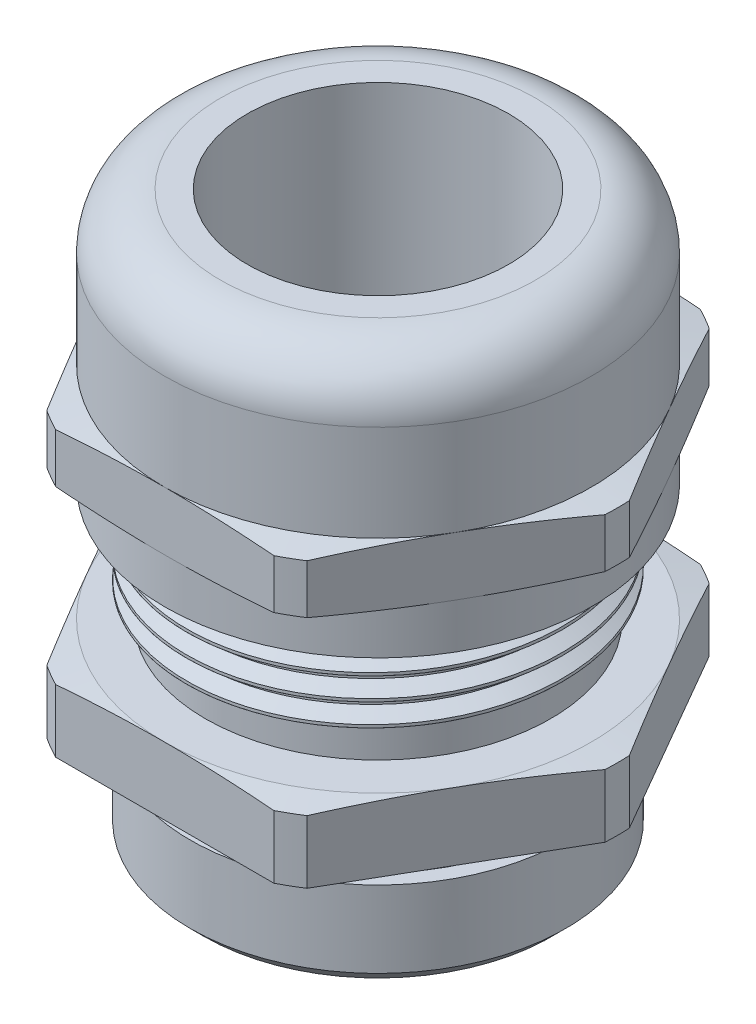
SolidWorks part; units mm, degrees
note: '?' marks a value the reader was unsure of.
material "Brass"
ref_plane "Front Plane" through (0, 0, 0) normal (0, 0, 1) x (1, 0, 0)
ref_plane "Top Plane" through (0, 0, 0) normal (0, 1, 0) x (1, 0, 0)
ref_plane "Right Plane" through (0, 0, 0) normal (1, 0, 0) x (0, 0, -1)
sketch "Sketch1" plane through (0, 0, 0) normal (0, 0, 1) x (1, 0, 0)
  line L0 (0, 0) -> (0, 40.2074) construction
  line L1 (-8.7, 34.6391) -> (-10.5, 34.6391)
  line L2 (-14.2, 30.9391) -> (-14.2, 24.5391)
  line L3 (-14.2, 24.5391) -> (-15.95, 24.2306)
  line L4 (-15.95, 24.2306) -> (-15.95, 20.9477)
  line L5 (-15.95, 20.9477) -> (-14.2, 20.6391)
  line L6 (-14.2, 20.6391) -> (-14.2, 17.6391)
  line L7 (-14.2, 17.6391) -> (-12.6, 17.6391)
  line L8 (-12.5, 19.6391) -> (-12.5, 11.8391)
  line L9 (-14.2, 9.8391) -> (-11.5, 9.8391)
  line L10 (-15.95, 9.5306) -> (-15.95, 5.3391)
  line L11 (-15.95, 5.3391) -> (-11.5, 5.3391)
  line L12 (-12.5, 3.3391) -> (-12.5, -2.6609)
  line L13 (-12.5, -2.6609) -> (-10, -2.6609)
  line L14 (-10, -2.6609) -> (-10, 15.0391)
  line L15 (-10, 15.0391) -> (-8.7, 15.0391)
  line L16 (-8.7, 15.0391) -> (-8.7, 34.6391)
  line L17 (-14.2, 9.8391) -> (-15.95, 9.5306)
  line L18 (-12.5, 11.8391) -> (-11.5, 11.8391)
  line L19 (-11.5, 11.8391) -> (-11.5, 9.8391)
  line L20 (-12.5, 3.3391) -> (-11.5, 3.3391)
  line L21 (-11.5, 3.3391) -> (-11.5, 5.3391)
  line L22 (-12.6, 17.6391) -> (-12.6, 19.6391)
  line L23 (-12.6, 19.6391) -> (-12.5, 19.6391)
  arc A0 (-10.5, 34.6391) -> (-14.2, 30.9391) centre (-10.5, 30.9391) ccw
  dimension "D11" = 3.7
  dimension "D3" = 31.9
  dimension "D4" = 28.4
  dimension "D5" = 17.4
  dimension "D8" = 3
  dimension "D9" = 3.9
  dimension "D10" = 37.3
  dimension "D12" = 10.1
  dimension "D13" = 25
  dimension "D14" = 20
  dimension "D15" = 4.5
  dimension "D16" = 17.7
  dimension "U-Cut 1" = 2
  dimension "Thread Depth" = 1
  dimension "U-Cut 2" = 2
  dimension "D19" = 0.1
  dimension "Thread Extend" = 2
  dimension "D21" = 7.8
revolve "Revolve1" add sketch "Sketch1" angle 360 about L0
sketch "Sketch2" plane through (0, 34.6391, 0) normal (0, 1, 0) x (1, 0, 0)
  line L1 (-16.3967, 0) -> (-8.1984, -14.2)
  line L2 (-8.1984, -14.2) -> (8.1984, -14.2)
  line L3 (8.1984, -14.2) -> (16.3967, 0)
  line L4 (16.3967, 0) -> (8.1984, 14.2)
  line L5 (8.1984, 14.2) -> (-8.1984, 14.2)
  line L6 (-8.1984, 14.2) -> (-16.3967, 0)
  circle A0 centre (0, 0) radius 14.2 construction
  circle A1 centre (0, 0) radius 14.2 construction
  circle A2 centre (0, 0) radius 33.2445
extrude "Extrude1" cut sketch "Sketch2" against normal through all
chamfer "Chamfer2" distance 0.9 angle 45 1 edges at (0, -2.6609, -12.5)
sketch "Sketch10" plane through (0, 11.8391, 0) normal (0, -1, 0) x (1, 0, 0)
  circle A0 centre (0, 0) radius 12.5
  dimension "D1" = 25
curve "Helix/Spiral1" pitch 1.5 height 9 turns 6
ref_plane "Plane1" through (-12.5, 20.8391, 0) normal (0, 0.0191, 0.9998) x (1, 0, 0)
sketch "Sketch11" plane through (-12.5, 20.8391, 0) normal (0, 0.0191, 0.9998) x (1, 0, 0)
  line L0 (0.0012, -8.9984) -> (0.0012, -10.3109) construction
  line L1 (0.9069, -9.5213) -> (0.9069, -9.788)
  line L2 (0.9069, -9.5213) -> (0.0012, -8.9984)
  line L3 (0.9069, -9.788) -> (0.0012, -10.3109)
  line L4 (-0.0854, -8.9484) -> (-0.0854, -10.3609)
  line L5 (0.0012, -8.9984) -> (-0.0854, -8.9484)
  line L6 (0.0012, -10.3109) -> (-0.0854, -10.3609)
  dimension "D1" = 1.3125
  dimension "D2" = 0.9057
  dimension "D3" = 60
  dimension "D4" = 60
  dimension "D5" = 0.1
sweep "Cut-Sweep1" cut profiles "Sketch11" path "Helix/Spiral1"
sketch "Sketch12" [suppressed] plane through (0, 43.6391, 0) normal (0, 1, 0) x (1, 0, 0)
  point P0 (0, 0)
sketch "Sketch13" [suppressed] plane through (0, -9.3609, 0) normal (0, -1, 0) x (1, 0, 0)
  point P0 (0, 0)
other "RPoint1" [suppressed]
other "RPoint2" [suppressed]
ref_axis "Axis1" [suppressed] through (0, 43.6391, 0) along (0, -1, 0)?
